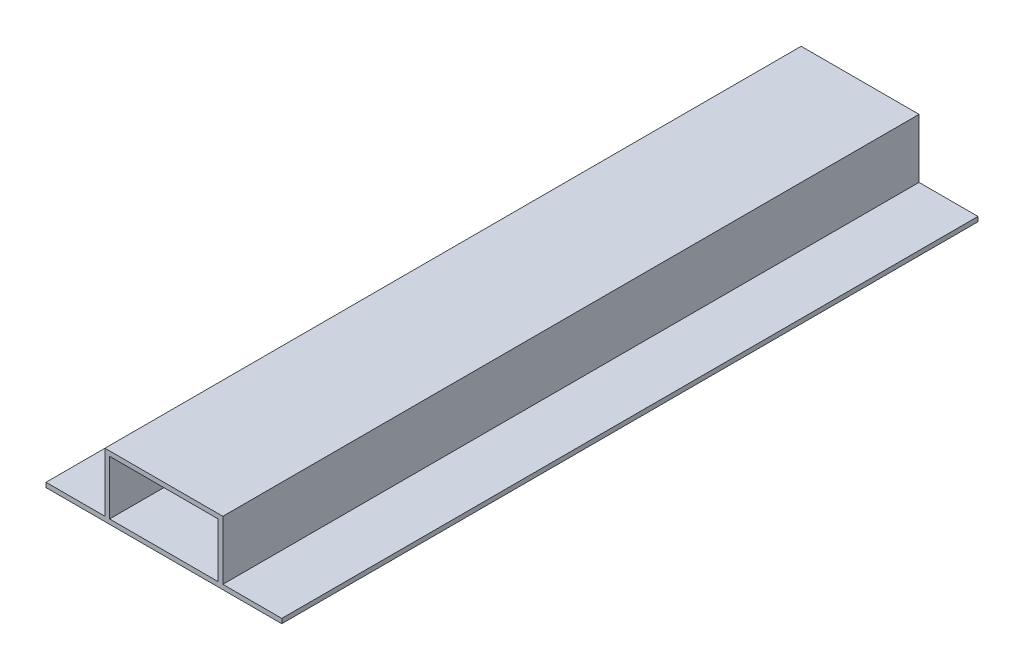
SolidWorks part; units mm, degrees
ref_plane "Alzado" through (0, 0, 0) normal (0, 0, 1) x (1, 0, 0)
ref_plane "Planta" through (0, 0, 0) normal (0, 1, 0) x (1, 0, 0)
ref_plane "Vista lateral" through (0, 0, 0) normal (1, 0, 0) x (0, 0, -1)
sketch "Croquis1" plane through (0, 0, 0) normal (0, 0, 1) x (1, 0, 0)
  line L0 (0, 31.0221) -> (0, -31.113) construction
  line L1 (38.9974, 0) -> (-46.5113, 0) construction
  line L2 (0, 12.7) -> (-11.7, 12.7)
  line L3 (0, 13.7) -> (-12.7, 13.7)
  line L4 (0, 13.7) -> (0, 1) construction
  line L5 (11.7, 1) -> (-11.7, 1)
  line L6 (-12.7, 13.7) -> (-12.7, 1)
  line L7 (25.4, 0) -> (-25.4, 0)
  line L8 (0, 0) -> (0, 1) construction
  line L9 (11.7, 1) -> (-11.7, 1)
  line L10 (-25.4, 0) -> (-25.4, 1)
  line L11 (-11.7, 12.7) -> (-11.7, 1)
  line L12 (-12.7, 1) -> (-25.4, 1)
  line L13 (12.7, 1) -> (25.4, 1)
  line L14 (11.7, 12.7) -> (11.7, 1)
  line L15 (25.4, 0) -> (25.4, 1)
  line L16 (12.7, 13.7) -> (12.7, 1)
  line L17 (0, 13.7) -> (12.7, 13.7)
  line L18 (0, 12.7) -> (11.7, 12.7)
  dimension "D1" = 12.7
  dimension "D2" = 12.7
  dimension "D3" = 1
  dimension "D4" = 1
  dimension "D5" = 25.4
extrude "Saliente-Extruir1" add sketch "Croquis1" along normal mid plane 150 contours L17 L3 L6 L12 L10 L7 L15 L13 L16 L2 L18 L14 L5 L11 region at (6.35, 13.1739, 0)
